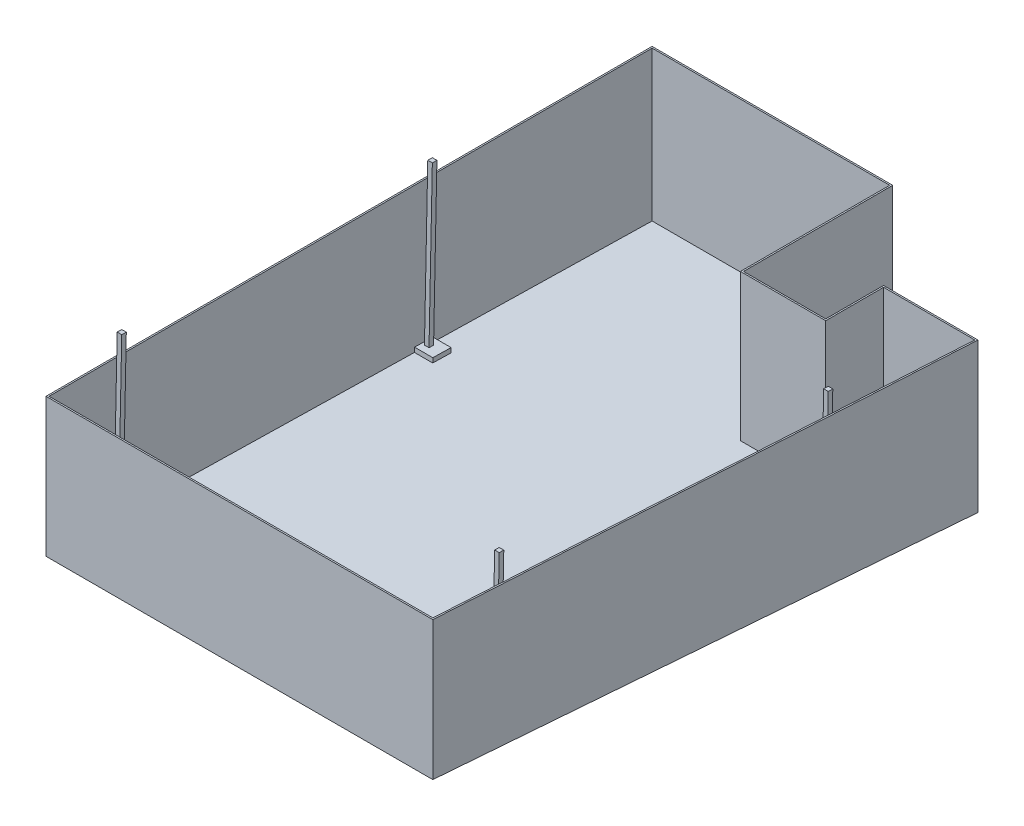
SolidWorks part; units mm, degrees
ref_plane "Front Plane" through (0, 0, 0) normal (0, 0, 1) x (1, 0, 0)
ref_plane "Top Plane" through (0, 0, 0) normal (0, 1, 0) x (1, 0, 0)
ref_plane "Right Plane" through (0, 0, 0) normal (1, 0, 0) x (0, 0, -1)
sketch "Sketch2" plane through (0, 0, 0) normal (0, 1, 0) x (1, 0, 0)
  line L0 (0, 5054.6) -> (0, -5054.6)
  line L1 (0, -5054.6) -> (6451.6, -5054.6)
  line L2 (6451.6, -5054.6) -> (6959.6, 3530.6)
  line L3 (4013.2, 5054.6) -> (0, 5054.6)
  line L4 (4013.2, 5054.6) -> (4013.2, 2565.4)
  line L5 (4013.2, 2565.4) -> (5384.8, 2565.4)
  line L6 (5384.8, 2565.4) -> (5384.8, 3530.6)
  line L7 (5384.8, 3530.6) -> (6959.6, 3530.6)
  point P16 (0, 0)
  dimension "D1" = 10109.2
  dimension "D2" = 4013.2
  dimension "D3" = 6451.6
  dimension "D4" = 2489.2
  dimension "D5" = 6959.6
  dimension "D6" = 965.2
  dimension "D7" = 1574.8
extrude "Boss-Extrude2" add sketch "Sketch2" along normal blind 2311.4 and the other way blind 254
sketch "Sketch4" plane through (0, 0, 0) normal (-1, 0, 0) x (0, 0, 1)
  line L0 (5054.6, 0) -> (-5054.6, -211.7576)
  line L1 (5054.6, -254) -> (5054.6, 2311.4) construction
  line L4 (-5054.6, -254) -> (-5054.6, 2311.4) construction
  line L5 (-5054.6, -211.7576) -> (-5054.6, -254)
  line L6 (-5054.6, -254) -> (5054.6, -254)
  line L7 (5054.6, -254) -> (5054.6, 0)
  dimension "D1" = 1.2
extrude "Cut-Extrude1" cut sketch "Sketch4" against normal through all
shell "Shell3" thickness 25.4 removed face at (4025.9, 2311.4, -1524)
sketch "Sketch5" plane through (0, -80.4379, 1.6849) normal (0, 0.9998, -0.0209) x (1, 0, 0)
  line L1 (25.4, -4114.2179) -> (330.2, -4114.2179)
  line L2 (330.2, -4114.2179) -> (330.2, -3809.4179)
  line L3 (330.2, -3809.4179) -> (25.4, -3809.4179)
  line L4 (6427.6585, -5028.6179) -> (25.4, -5028.6179) construction
  line L5 (25.4, -5028.6179) -> (25.4, 5031.9885) construction
  line L10 (25.4, 1067.3821) -> (330.2, 1067.3821)
  line L15 (330.2, 1067.3821) -> (330.2, 1372.1821)
  line L16 (330.2, 1372.1821) -> (25.4, 1372.1821)
  line L17 (6501.521, 1067.3821) -> (6788.2895, 1067.3821)
  line L18 (25.4, 1372.1821) -> (25.4, 1067.3821)
  line L19 (25.4, -4114.2179) -> (25.4, -3809.4179)
  line L20 (6194.4518, -4114.2179) -> (6481.7532, -4114.2179)
  line L22 (6499.7847, -3809.4179) -> (6194.4518, -3809.4179)
  line L23 (6194.4518, -4114.2179) -> (6194.4518, -3809.4179)
  line L25 (6932.6526, 3507.6542) -> (6427.6585, -5028.6179) construction
  line L26 (6806.321, 1372.1821) -> (6501.521, 1372.1821)
  line L27 (6501.521, 1067.3821) -> (6501.521, 1372.1821)
  line L28 (6806.321, 1372.1821) -> (6788.2895, 1067.3821)
  line L29 (6499.7847, -3809.4179) -> (6481.7532, -4114.2179)
  dimension "D1" = 304.8
  dimension "D2" = 914.4
  dimension "D3" = 304.8
  dimension "D4" = 304.8
  dimension "D5" = 304.8
  dimension "D7" = 5181.6
  dimension "D8" = 304.8
extrude "Boss-Extrude4" add sketch "Sketch5" along normal blind 76.2
sketch "Sketch6" plane through (0, -4.2546, 0.0891) normal (0, 0.9998, -0.0209) x (1, 0, 0)
  line L0 (76.2, 1257.8821) -> (76.2, 1181.6821)
  line L1 (76.2, 1181.6821) -> (152.4, 1181.6821)
  line L2 (152.4, 1181.6821) -> (152.4, 1257.8821)
  line L3 (152.4, 1257.8821) -> (76.2, 1257.8821)
  line L4 (76.2, -3923.7179) -> (76.2, -3999.9179)
  line L5 (76.2, -3999.9179) -> (152.4, -3999.9179)
  line L6 (152.4, -3999.9179) -> (152.4, -3923.7179)
  line L7 (152.4, -3923.7179) -> (76.2, -3923.7179)
  line L8 (6372.2518, -3923.7179) -> (6372.2518, -3999.9179)
  line L9 (6372.2518, -3999.9179) -> (6448.4518, -3999.9179)
  line L10 (6448.4518, -3999.9179) -> (6448.4518, -3923.7179)
  line L11 (6448.4518, -3923.7179) -> (6372.2518, -3923.7179)
  line L12 (6679.321, 1257.8821) -> (6679.321, 1181.6821)
  line L13 (6679.321, 1181.6821) -> (6755.521, 1181.6821)
  line L14 (6755.521, 1181.6821) -> (6755.521, 1257.8821)
  line L15 (6755.521, 1257.8821) -> (6679.321, 1257.8821)
  line L16 (330.2, 1067.3821) -> (330.2, 1372.1821) construction
  line L17 (330.2, -4114.2179) -> (330.2, -3809.4179) construction
  line L18 (25.4, 1372.1821) -> (25.4, 1067.3821) construction
  line L21 (6194.4518, -3809.4179) -> (6194.4518, -4114.2179) construction
  line L22 (6501.521, 1372.1821) -> (6501.521, 1067.3821) construction
  point P18 (330.2, 1219.7821)
  point P19 (152.4, 1219.7821)
  point P20 (6679.321, 1219.7821)
  point P23 (330.2, -3961.8179)
  point P24 (152.4, -3961.8179)
  point P25 (6372.2518, -3961.8179)
  dimension "D1" = 76.2
  dimension "D2" = 50.8
  dimension "D3" = 177.8
  dimension "D4" = 177.8
sketch3d "3DSketch1"
  point P0 (5144.6677, 2311.4, 5044.2382)
ref_plane "Plane3" through (0, 2313.94, 0) normal (0, 1, 0) x (1, 0, 0)
extrude "Boss-Extrude6" add sketch "Sketch6" along normal blind 2643.378
